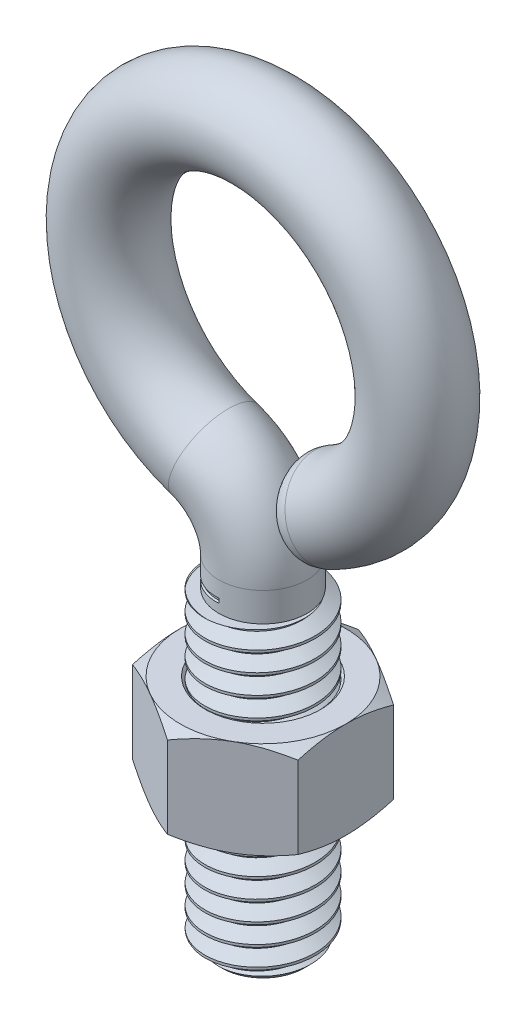
SolidWorks part; units mm, degrees
note: '?' marks a value the reader was unsure of.
ref_plane "Front Plane" through (0, 0, 0) normal (0, 0, 1) x (1, 0, 0)
ref_plane "Top Plane" through (0, 0, 0) normal (0, 1, 0) x (1, 0, 0)
ref_plane "Right Plane" through (0, 0, 0) normal (1, 0, 0) x (0, 0, -1)
sketch "Sketch1" plane through (0, 0, 0) normal (0, 0, 1) x (1, 0, 0)
  line L0 (0, -14.2875) -> (0, -39.6875) construction
  line L1 (-3.9687, -39.6875) -> (3.9688, -39.6875) construction
  line L2 (0, -17.4625) -> (3.9688, -17.4625) construction
  line L3 (0, -14.2875) -> (0, -7.9375) construction
  line L4 (-3.175, -17.4625) -> (3.175, -17.4625) construction
  line L5 (3.175, -17.4625) -> (3.175, -14.2875) construction
  line L6 (-3.9687, -39.6875) -> (-3.9687, -38.2764) construction
  line L7 (3.9688, -39.6875) -> (3.9688, -17.4625) construction
  line L8 (3.175, -14.2875) -> (0, -14.2875) construction
  circle A0 centre (0, 0) radius 14.2875 construction
  circle A1 centre (0, 11.1125) radius 3.175 construction
  circle A2 centre (0, 0) radius 7.9375 construction
  point P9 (0, -14.2875)
  point P10 (0, 14.2875)
  point P11 (0, 7.9375)
  point P14 (0, -39.6875)
  point P22 (0, -14.2875)
  point P24 (0, -17.4625)
  point P27 (-3.9687, -39.6875)
  point P28 (3.9688, -39.6875)
  point P30 (-3.175, -17.4625)
  point P31 (-3.175, -20.9903)
  dimension "Pitch" = 1.4111
  dimension "A" = 6.35
  dimension "Eye Dia." = 15.875
  dimension "Shank Lg." = 25.4
  dimension "Thread OD" = 7.9375
  dimension "Thread Lg." = 22.225
  dimension "Overall Lg." = 53.975
  dimension "Wire OD." = 6.35
  dimension "OD" = 28.575
  dimension "D1" = 3.5278
sketch "Sketch2" plane through (0, 0, 0) normal (0, 1, 0) x (1, 0, 0)
  circle A0 centre (0, 0) radius 3.9688
extrude "Boss-Extrude1" add sketch "Sketch2" against normal up to vertex (39.6875 mm away) from vertex at -17.4625 starting at point (0, -17.4625, 0)
sketch "Sketch3" plane through (0, -39.6875, 0) normal (0, -1, 0) x (1, 0, 0)
  circle A1 centre (0, 0) radius 3.9688
  circle A2 centre (0, 0) radius 3.9688
  point P0 (3.9688, 0)
  point P1 (0, -3.9688)
  dimension "D1" = 0
sketch "Sketch7" plane through (0, -17.4625, 0) normal (0, 1, 0) x (1, 0, 0)
  circle A0 centre (0, 0) radius 3.175
sketch "Sketch8" plane through (0, 0, 0) normal (0, 0, 1) x (1, 0, 0)
  line L1 (0, -15.375) -> (0, -17.4625)
  line L2 (0, -14.2875) -> (0, -7.9375) construction
  line L3 (0, -14.2875) -> (0, -39.6875) construction
  line L4 (-5.08, -15.375) -> (-0.9628, -12.3992) construction
  arc A0 (3.1424, -10.6589) -> (-3.4863, -10.5515) centre (0, 0) ccw
  arc A1 (-3.4863, -10.5515) -> (0, -15.375) centre (-5.08, -15.375) cw
  circle A3 centre (0, -11.1125) radius 3.175 construction
sweep "Sweep1" add profiles "Sketch7" path "Sketch8"
fillet "Fillet1" radius 1.9844 1 edges at (3.1424, -10.6589, 3.175)
chamfer "Chamfer1" distance 1.0319 angle 45 1 edges at (0, -39.6875, 3.9688)
sketch "Sketch9" plane through (0, -39.6875, 0) normal (0, -1, 0) x (1, 0, 0)
  line L1 (0, 6.8741) -> (-5.9531, 3.437)
  line L2 (-5.9531, 3.437) -> (-5.9531, -3.437)
  line L3 (-5.9531, -3.437) -> (0, -6.8741)
  line L4 (0, -6.8741) -> (5.9531, -3.437)
  line L5 (5.9531, -3.437) -> (5.9531, 3.437)
  line L6 (5.9531, 3.437) -> (0, 6.8741)
  circle A0 centre (0, 0) radius 5.9531 construction
  circle A1 centre (0, 0) radius 3.9688
extrude "Boss-Extrude2" add sketch "Sketch9" against normal blind 6.9453 from offset 9.779 separate body offset against normal yes
sketch "Sketch10" plane through (0, 0, 0) normal (1, 0, 0) x (0, 0, -1)
  line L0 (-5.9531, -22.9632) -> (-7.795, -22.9632)
  line L1 (-7.795, -22.9632) -> (-7.795, -29.9085)
  line L2 (-7.795, -29.9085) -> (-5.9531, -29.9085)
  line L3 (-5.9531, -29.9085) -> (-6.8741, -29.3768)
  line L4 (-6.8741, -29.3768) -> (-6.8741, -23.4949)
  line L5 (-6.8741, -23.4949) -> (-5.9531, -22.9632)
  line L6 (-3.7924, -22.9632) -> (-3.7924, -29.9085)
  line L7 (-3.7924, -29.9085) -> (-4.1451, -29.9085)
  line L8 (-4.1451, -29.9085) -> (-3.9688, -29.7321)
  line L9 (-3.9688, -29.7321) -> (-3.9688, -23.1396)
  line L10 (-3.9688, -23.1396) -> (-4.1451, -22.9632)
  line L11 (-4.1451, -22.9632) -> (-3.7924, -22.9632)
  line L12 (-3.9688, -22.9632) -> (-3.9688, -29.9085) construction
  line L14 (-3.9688, -29.7321) -> (-3.9688, -29.9085) construction
  line L15 (-3.9688, -23.1396) -> (-3.9688, -22.9632) construction
  line L16 (-6.8741, -22.9632) -> (-6.8741, -29.9085) construction
  line L18 (-5.9531, -29.9085) -> (-5.9531, -39.6875) construction
  dimension "D1" = 60
  dimension "D2" = 45
  dimension "D3" = 0.1764
revolve "Cut-Revolve1" cut sketch "Sketch10" angle 360 about L0
ref_axis "Center Axis 1" through (0, -14.2875, 0) along (0, -1, 0)?
curve "Helix/Spiral1" pitch 1.4111 height 23.6361 turns 16.75 parameters "Pitch"=1.4111
sketch "Sketch4" plane through (0, 0, 0) normal (0, 0, 1) x (1, 0, 0)
  line L0 (4.1215, -39.5993) -> (4.1215, -41.0104) construction
  line L1 (4.1215, -41.0104) -> (2.8994, -40.3049) construction
  line L2 (2.8994, -40.3049) -> (4.1215, -39.5993) construction
  line L3 (3.0522, -40.2167) -> (3.0522, -40.3931) construction
  line L4 (3.9688, -39.6875) -> (3.9688, -40.9222) construction
  line L5 (2.8994, -40.3049) -> (3.0522, -40.3049) construction
  line L6 (3.9688, -40.3049) -> (4.1215, -40.3049) construction
  line L7 (4.0451, -39.6434) -> (3.0522, -40.2167)
  line L8 (3.0522, -40.2167) -> (3.0522, -40.3931)
  line L9 (3.0522, -40.3931) -> (4.0451, -40.9663)
  line L10 (4.0451, -40.9663) -> (4.0451, -39.6434)
  point P13 (4.0451, -40.3049)
  dimension "D2" = 0.1764
sweep "Cut-Sweep1" cut profiles "Sketch4" path "Helix/Spiral1"
sketch "SketchX" plane through (0, 0, 0) normal (1, 0, 0) x (0, 0, -1)
  line L0 (3.9688, -39.6875) -> (3.9688, -22.7542) construction
  dimension "D1" = 16.9333
equation "\"D3@Helix/Spiral1\" = \"Pitch@Helix/Spiral1\" + \"Thread Lg.@Sketch1\""
equation "\"D1@Sketch4\" = \"Pitch@Helix/Spiral1\""
equation "\"A@Sketch1\" = \"Wire OD.@Sketch1\""
equation "\"D2@Sketch4\" = \"D1@Sketch4\" / 8"
equation "\"D1@Fillet1\" = \"Thread OD@Sketch1\" / 4"
equation "\"D1@SketchX\" = \"Thread Lg.@Sketch1\" -  ( \"Pitch@Helix/Spiral1\" *  4 ) +  ( \"Pitch@Helix/Spiral1\" /  4 ) "
equation "\"Nut Wd.@Sketch9\" = \"Thread OD@Sketch1\" * 1.5"
equation "\"Nut Ht.@Boss-Extrude2\" = \"Thread OD@Sketch1\" * 0.875"
equation "\"Offset@Boss-Extrude2\"=\"Thread Lg.@Sketch1\"*.44"
equation "\"D3@Sketch10\" = \"Pitch@Helix/Spiral1\" / 8"
equation "\"D1@Chamfer1\"=\"Thread OD@Sketch1\"*.13"
equation "\"D1@Sketch8\"=\"Shank Lg.@Sketch1\"*.2"
equation "\"Pitch@Helix/Spiral1\"=\"Pitch@Sketch1\""
equation "\"D1@Sketch1\"=\"Pitch@Sketch1\"*2.5"
